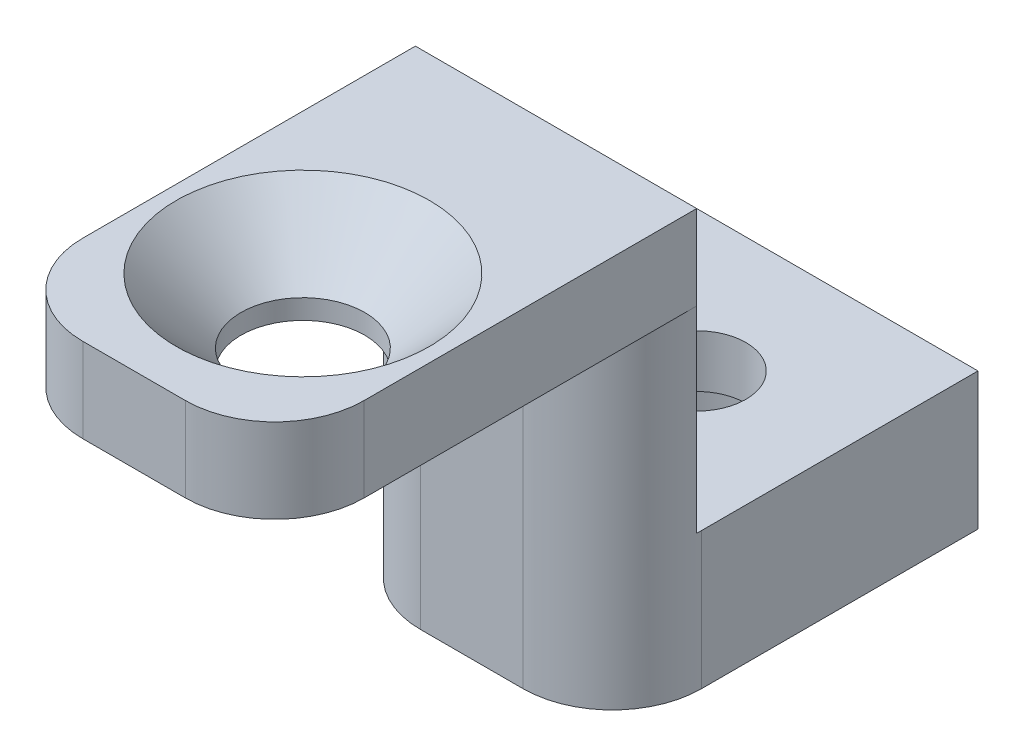
SolidWorks part; units mm, degrees
material "ABS"
ref_plane "Front Plane" through (0, 0, 0) normal (0, 0, 1) x (1, 0, 0)
ref_plane "Top Plane" through (0, 0, 0) normal (0, 1, 0) x (1, 0, 0)
ref_plane "Right Plane" through (0, 0, 0) normal (1, 0, 0) x (0, 0, -1)
sketch "Sketch1" plane through (0, 0, 0) normal (1, 0, 0) x (0, 0, -1)
  line L0 (-12, 0) -> (0, 0)
  line L1 (0, 0) -> (0, -11.87)
  line L2 (0, -11.87) -> (13, -11.87)
  line L3 (13, -11.87) -> (13, -7)
  line L4 (13, -7) -> (3, -7)
  line L5 (3, -7) -> (3, 3)
  line L6 (3, 3) -> (-12, 3)
  line L7 (-12, 3) -> (-12, 0)
  dimension "D1" = 4.87
  dimension "D2" = 3
  dimension "D3" = 3
  dimension "D4" = 10
  dimension "D5" = 12
  dimension "D6" = 10
extrude "Boss-Extrude1" add sketch "Sketch1" along normal mid plane 10
sketch "Sketch2" plane through (0, -11.87, 0) normal (0, 1, 0) x (1, 0, 0)
  line L0 (0, 3) -> (0, 13) construction
  line L1 (5, 3) -> (-5, 3) construction
  line L2 (5, 13) -> (-5, 13) construction
  point P6 (0, 8)
sketch "Sketch3" plane through (0, 3, 0) normal (0, 1, 0) x (1, 0, 0)
  line L0 (0, -12) -> (0, 0) construction
  line L1 (5, -12) -> (-5, -12) construction
  line L3 (5, 0) -> (-5, 0) construction
  point P6 (0, -6)
sketch "Sketch4" plane through (0, 0, 0) normal (1, 0, 0) x (0, 0, -1)
  line L0 (-6, 3) -> (-10.5, 3)
  line L1 (-12, 3) -> (0, 3) construction
  line L2 (-10.5, 3) -> (-8.2, 0.7)
  line L5 (-6, 0) -> (-6, 3)
  line L8 (-8.2, 0.7) -> (-8.2, 0)
  line L9 (-8.2, 0) -> (-6, 0)
  line L11 (-12, 0) -> (0, 0) construction
  dimension "D1" = 45
  dimension "D2" = 2.2
  dimension "D3" = 4.5
  dimension "D4" = 3
  dimension "D5" = 2.3
revolve "Cut-Revolve1" cut sketch "Sketch4" angle 360 about L5
sketch "Sketch5" plane through (0, 0, 0) normal (1, 0, 0) x (0, 0, -1)
  line L0 (8, -11.87) -> (8, -7)
  line L1 (3, -11.87) -> (13, -11.87) construction
  line L2 (8, -7) -> (9.75, -7)
  line L3 (9.75, -7) -> (9.75, -8.87)
  line L4 (9.75, -8.87) -> (11.2, -8.87)
  line L5 (11.2, -8.87) -> (11.2, -11.87)
  line L6 (11.2, -11.87) -> (8, -11.87)
  line L7 (13, -7) -> (3, -7) construction
  dimension "D1" = 3.2
  dimension "D2" = 3
  dimension "D3" = 1.75
revolve "Cut-Revolve2" cut sketch "Sketch5" angle 360 about L0
fillet "Fillet2" radius 3.175 4 edges at (-5, 1.5, 12) (5, 1.5, 12) (-5, -5.935, 0) (5, -5.935, 0)
